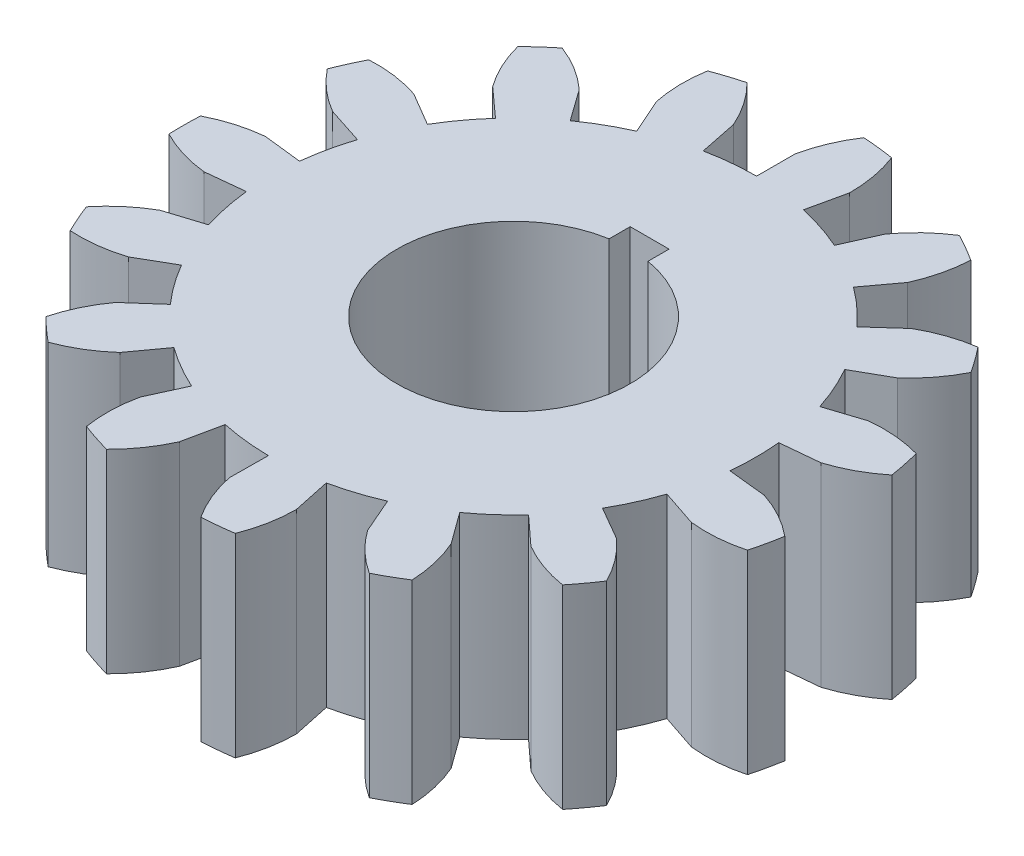
SolidWorks part; units mm, degrees
ref_plane "Front Plane" through (0, 0, 0) normal (0, 0, 1) x (1, 0, 0)
ref_plane "Top Plane" through (0, 0, 0) normal (0, 1, 0) x (1, 0, 0)
ref_plane "Right Plane" through (0, 0, 0) normal (1, 0, 0) x (0, 0, -1)
sketch "Sketch1" plane through (0, 0, 0) normal (0, 1, 0) x (1, 0, 0)
  circle A3 centre (0, 0) radius 6.25
  circle A4 centre (0, 0) radius 8.5
  circle A5 centre (0, 0) radius 7.5
  circle A6 centre (0, 0) radius 6.5
  circle A7 centre (0, 0) radius 7.2444
  dimension "pitch circle" = 15
  dimension "addendum circle" = 17
  dimension "root circle" = 12.5
  dimension "clearance circle" = 13
  dimension "base circle" = 14.4889
sketch "Sketch2" plane through (0, 0, 0) normal (0, 1, 0) x (1, 0, 0)
  line L0 (0, 0) -> (0, 7.2444)
  line L1 (0, 0) -> (3.6222, 6.2739) construction
  line L2 (0, 0) -> (6.2739, 3.6222) construction
  line L3 (0, 0) -> (7.2444, 0) construction
  line L4 (7.2444, 0) -> (7.2444, 11.3795) construction
  line L5 (6.2739, 3.6222) -> (2.4807, 10.1922) construction
  line L6 (3.6222, 6.2739) -> (0.3372, 8.1705) construction
  line L7 (0, 0) -> (3.0505, 6.8516)
  line L8 (0, 0) -> (1.5593, 7.3361) construction
  line L9 (0.8161, 7.4555) -> (0, 0) construction
  circle A0 centre (0, 0) radius 7.2444 construction
  circle A1 centre (0, 0) radius 7.5 construction
  arc A2 (1.5593, 7.3361) -> (0.0647, 7.4997) centre (0, 0) ccw
  spline S0 degree 3 poles (0, 7.2444) (0.6373, 10.2112) (4.7997, 11.3834) (7.2444, 11.3795) knots 0 0 0 0 1 1 1 1
  spline S1 degree 3 poles (1.5673, 7.0729) (1.5869, 10.1072) (-2.2234, 12.1522) (-4.611, 12.6773) knots 0 0 0 0 1 1 1 1
  point P11 (0, 0)
  dimension "Involute Control" = 90
  dimension "Base circle quarter circumference" = 11.3795
  dimension "D1" = 7.5864
  dimension "D2" = 3.7932
  dimension "pitch circle" = 24
  dimension "Involute array" = 4
sketch "Sketch3" plane through (0, 0, 0) normal (0, 1, 0) x (1, 0, 0)
  line L0 (1.5673, 7.0729) -> (1.3521, 6.102)
  line L1 (0, 0) -> (0, 7.2444) construction
  line L3 (0, 6.25) -> (0, 7.2444)
  arc A1 (0.5223, 8.4839) -> (0, 7.2444) centre (3.5325, 6.4857) ccw
  circle A2 centre (0, 0) radius 8.5 construction
  circle A3 centre (0, 0) radius 6.25 construction
  arc A7 (1.5673, 7.0729) -> (1.3255, 8.396) centre (-2.0457, 7.0963) ccw
  arc A8 (1.3521, 6.102) -> (0, 6.25) centre (0, 0) ccw
  arc A9 (1.3255, 8.396) -> (0.5223, 8.4839) centre (0, 0) ccw
  circle A10 centre (0, 0) radius 7.2444 construction
  spline S0 degree 3 poles (1.5673, 7.0729) (1.5869, 10.1072) (-2.2234, 12.1522) (-4.611, 12.6773) knots 0 0 0 0 1 1 1 1 construction
  spline S1 degree 3 poles (0, 7.2444) (0.6373, 10.2112) (4.7997, 11.3834) (7.2444, 11.3795) knots 0 0 0 0 1 1 1 1 construction
extrude "Boss-Extrude1" add sketch "Sketch3" along normal blind 5
sketch "Sketch5" plane through (0, 0, 0) normal (1, 0, 0) x (0, 0, -1)
  line L0 (0, 0) -> (0, 5.4709) construction
pattern_circular "CirPattern4" count 15 over 360 about axis through (0, 0, 0) along (0, 1, 0) reverse direction yes of bodies 101
sketch "Sketch6" plane through (0, 0, 0) normal (0, 1, 0) x (1, 0, 0)
  circle A0 centre (0, 0) radius 6.25 construction
  circle A1 centre (0, 0) radius 6.25
extrude "Boss-Extrude2" add sketch "Sketch6" along normal up to surface (5 mm away) up to face at (-2.2305, 5, -6.967)
sketch "Sketch7" plane through (0, 5, 0) normal (0, 1, 0) x (1, 0, 0)
  line L1 (-0.5, 3.5) -> (0.5, 3.5)
  line L2 (-0.5, 3.5) -> (-0.5, 2.5)
  line L3 (-0.5, 2.5) -> (0.5, 2.5)
  line L4 (0.5, 3.5) -> (0.5, 2.5)
  line L5 (-0.5, 3.5) -> (0.5, 2.5) construction
  line L6 (-0.5, 2.5) -> (0.5, 3.5) construction
  circle A0 centre (0, 0) radius 3
  point P3 (0, 3)
  dimension "D1" = 6
  dimension "D2" = 1
extrude "Cut-Extrude1" cut sketch "Sketch7" against normal through all contours L2 A0 L4 L3 | L4 A0 L2 L3 | L4 L3 L2 L1 region at (0, 5, -2.7432) region at (0, 5, 0.048)
equation "\"Module\"= 1"
equation "\"Teeth number\"= 15"
equation "\"Pressure angle\"= 15"
equation "\"pitch circle@Sketch1\"= \"Module\" * \"Teeth number\""
equation "\"addendum circle@Sketch1\"= \"pitch circle@Sketch1\" + ( \"Module\" * 2 )"
equation "\"root circle@Sketch1\"= \"pitch circle@Sketch1\" - ( ( \"Module\" * 1.25 ) * 2 )"
equation "\"clearance circle@Sketch1\"= \"pitch circle@Sketch1\" - ( \"Module\" * 2 )"
equation "\"base circle@Sketch1\"= \"pitch circle@Sketch1\" * cos ( \"Pressure angle\" )"
equation "\"D1@Sketch2\"=\"Base circle quarter circumference@Sketch2\"/3*2"
equation "\"D2@Sketch2\"=\"Base circle quarter circumference@Sketch2\"/3"
equation "\"pitch circle@Sketch2\"=360/\"Teeth number\""
equation "\"D1@CirPattern4\"=\"Teeth number\""
equation "\"Base circle quarter circumference@Sketch2\"= \"base circle@Sketch1\" * pi / 4"
